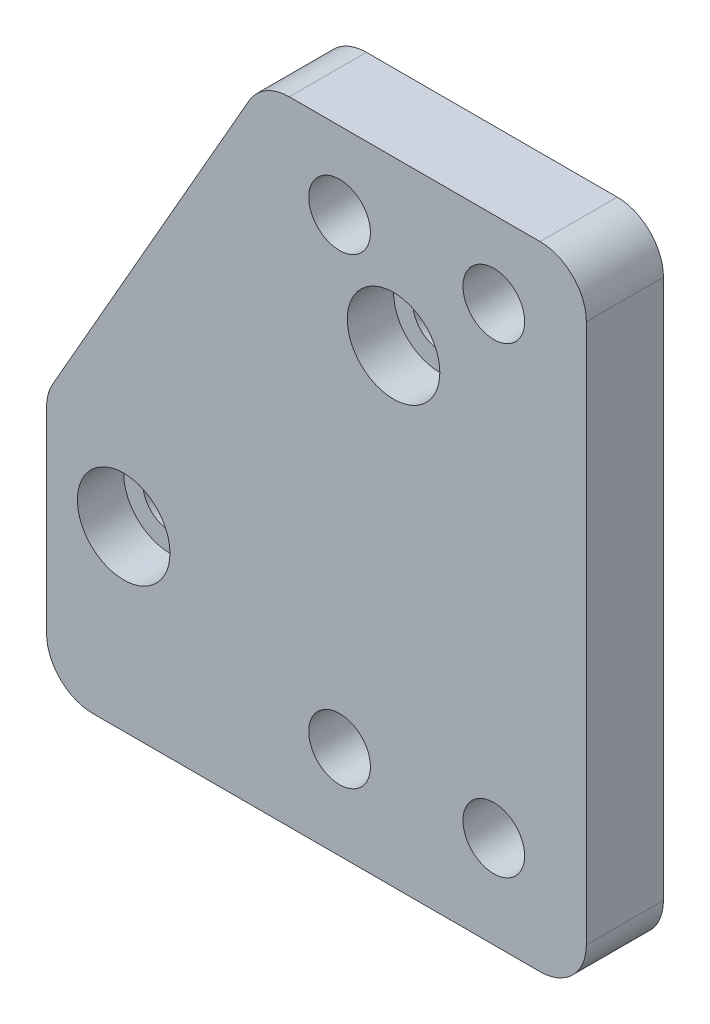
SolidWorks part; units mm, degrees
ref_plane "Front Plane" through (0, 0, 0) normal (0, 0, 1) x (1, 0, 0)
ref_plane "Top Plane" through (0, 0, 0) normal (0, 1, 0) x (1, 0, 0)
ref_plane "Right Plane" through (0, 0, 0) normal (1, 0, 0) x (0, 0, -1)
sketch "Sketch2" plane through (0, 0, 0) normal (0, 0, 1) x (1, 0, 0)
  line L0 (-24, -4.5) -> (-10, 20)
  line L1 (-32, 23.75) -> (32, 23.75) construction
  line L2 (-32, 23.75) -> (-32, -23.75) construction
  line L3 (-32, -23.75) -> (32, -23.75) construction
  line L4 (32, 23.75) -> (32, -23.75) construction
  line L5 (-32, 23.75) -> (32, -23.75) construction
  line L6 (-32, -23.75) -> (32, 23.75) construction
  line L7 (11, -21) -> (11, 20)
  line L8 (-24, -21) -> (11, -21)
  line L9 (-10, 20) -> (11, 20)
  line L10 (-5, 15) -> (5, 15) construction
  line L11 (-5, 15) -> (-5, -15) construction
  line L12 (-5, -15) -> (5, -15) construction
  line L13 (5, 15) -> (5, -15) construction
  line L14 (-5, 15) -> (5, -15) construction
  line L15 (-5, -15) -> (5, 15) construction
  line L16 (-24, -4.5) -> (-24, -21)
  circle A0 centre (-1.5, 9.4) radius 1.75
  circle A1 centre (-19, -9.5) radius 1.75
  circle A4 centre (-5, 15) radius 2
  circle A5 centre (-5, -15) radius 2
  circle A6 centre (5, 15) radius 2
  circle A7 centre (5, -15) radius 2
  point P0 (0, 0)
  point P10 (-19, -21.6656)
  point P17 (-21.8675, -4.9888)
  point P19 (-28.0692, -21.6656)
  point P23 (0, 0)
  point P24 (0, 0)
  point P27 (-28.0692, -21.9576)
  point P28 (-21.8675, -21)
  point P30 (-24.3302, -3.2095)
  point P31 (-8.872, 21)
  point P32 (-10.1154, 20)
  point P33 (-24, -6.0151)
  dimension "D1" = 30.5
  dimension "D2" = 3.5
  dimension "D5" = 4
  dimension "D6" = 64
  dimension "D7" = 47.5
  dimension "D8" = 14.25
  dimension "D13" = 6
  dimension "D3" = 17.5
  dimension "D4" = 18.9
  dimension "D9" = 6
  dimension "D10" = 10
  dimension "D11" = 30
  dimension "D12" = 5
  dimension "D14" = 5
  dimension "D15" = 5
  dimension "D16" = 5
extrude "Boss-Extrude1" add sketch "Sketch2" along normal blind 5
sketch "Sketch3" plane through (0, 0, 5) normal (0, 0, 1) x (1, 0, 0)
  circle A0 centre (-1.5, 9.4) radius 3
  circle A1 centre (-19, -9.5) radius 3
  dimension "D1" = 6
  dimension "D2" = 6
extrude "Cut-Extrude1" cut sketch "Sketch3" against normal blind 3
fillet "Fillet1" radius 3 5 edges at (-24, -4.5, 2.5) (-10, 20, 2.5) (11, 20, 2.5) (11, -21, 2.5) (-24, -21, 2.5)
